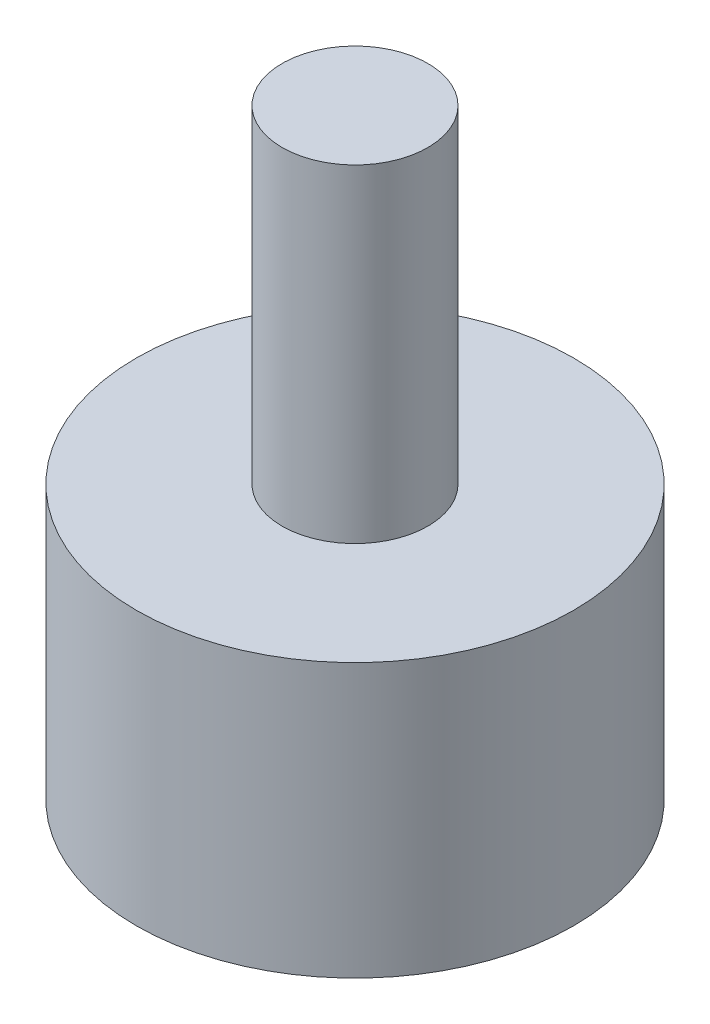
SolidWorks part; units mm, degrees
ref_plane "Front Plane" through (0, 0, 0) normal (0, 0, 1) x (1, 0, 0)
ref_plane "Top Plane" through (0, 0, 0) normal (0, 1, 0) x (1, 0, 0)
ref_plane "Right Plane" through (0, 0, 0) normal (1, 0, 0) x (0, 0, -1)
sketch "Sketch1" plane through (0, 0, 0) normal (0, 1, 0) x (1, 0, 0)
  circle A0 centre (0, 0) radius 12
  dimension "D1" = 24
extrude "Boss-Extrude1" add sketch "Sketch1" along normal blind 15
sketch "Sketch2" plane through (0, 15, 0) normal (0, 1, 0) x (1, 0, 0)
  circle A0 centre (0, 0) radius 4
  dimension "D1" = 8
extrude "Boss-Extrude2" add sketch "Sketch2" along normal blind 18
sketch "Sketch4" plane through (0, 0, 0) normal (0, -1, 0) x (1, 0, 0)
  circle A0 centre (0, 0) radius 8
  dimension "D1" = 16
extrude "Cut-Extrude1" cut sketch "Sketch4" against normal blind 2
dome "Dome1" faces to dome 1 distance 8 reverse direction no elliptical dome no face at (0, 2, -8) parameters "D1"=8
sketch "Sketch5" plane through (0, 0, 0) normal (0, -1, 0) x (1, 0, 0)
  circle A0 centre (0, 0) radius 7.5
  circle A1 centre (0, 0) radius 10.75
  dimension "D1" = 21.5
  dimension "D2" = 15
extrude "Boss-Extrude3" add sketch "Sketch5" along normal blind 1.5
chamfer "Chamfer1" distance 2 angle 60 1 edges at (0, -1.5, -10.75) first distance on face at (0, -1.5, -10.75)
